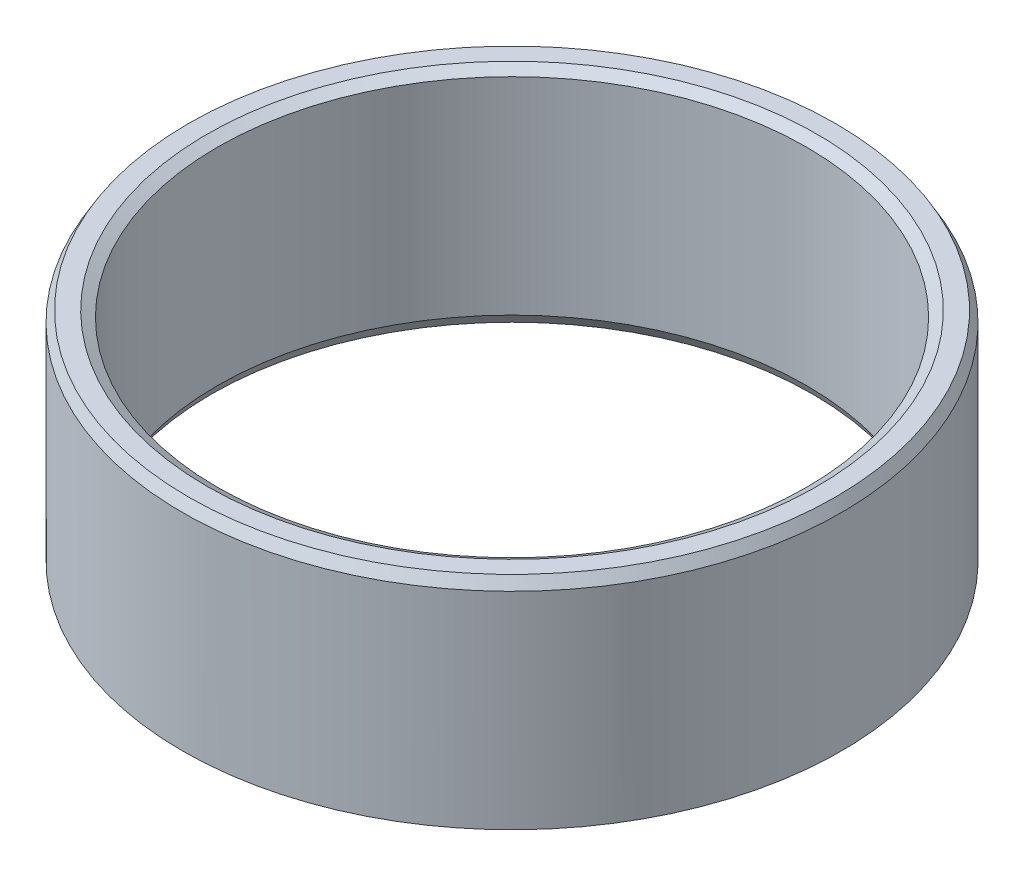
SolidWorks part; units mm, degrees
ref_plane "Front Plane" through (0, 0, 0) normal (0, 0, 1) x (1, 0, 0)
ref_plane "Top Plane" through (0, 0, 0) normal (0, 1, 0) x (1, 0, 0)
ref_plane "Right Plane" through (0, 0, 0) normal (1, 0, 0) x (0, 0, -1)
sketch "Sketch1" plane through (0, 0, 0) normal (0, 1, 0) x (1, 0, 0)
  circle A0 centre (0, 0) radius 45
  dimension "SLEEVE_OD" = 90
extrude "Boss-Extrude1" add sketch "Sketch1" along normal blind 30.4411
sketch "Sketch2" plane through (0, 0, 0) normal (0, 1, 0) x (1, 0, 0)
  circle A0 centre (0, 0) radius 40.2276
  dimension "BORE_D" = 80.4552
extrude "Cut-Extrude1" cut sketch "Sketch2" along normal through all
chamfer "Chamfer1" distance 1.4231 angle 30 4 edges at (0, 30.4411, 40.2276) (0, 0, 40.2276) (0, 0, 45) (0, 30.4411, 45) first distance on face at (0, 30.4411, 40.2276) first distance on face at (0, 0, 40.2276) first distance on face at (0, 30.4411, 45)
